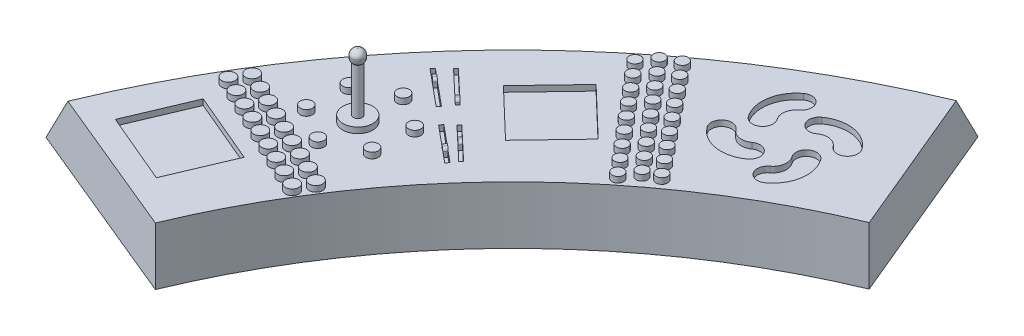
SolidWorks part; units mm, degrees
material "ABS"
ref_plane "Front Plane" through (0, 0, 0) normal (0, 0, 1) x (1, 0, 0)
ref_plane "Top Plane" through (0, 0, 0) normal (0, 1, 0) x (1, 0, 0)
ref_plane "Right Plane" through (0, 0, 0) normal (1, 0, 0) x (0, 0, -1)
sketch "Sketch1" plane through (0, 0, 0) normal (0, 1, 0) x (1, 0, 0)
  line L0 (0, 1495.54) -> (0, -1495.54) construction
  line L1 (0, 0) -> (1057.5065, 1057.5065) construction
  line L2 (1057.5065, 1057.5065) -> (-1057.5065, -1057.5065) construction
  line L3 (-1057.5065, -1057.5065) -> (1057.5065, -1057.5065) construction
  line L4 (1057.5065, -1057.5065) -> (-1057.5065, 1057.5065) construction
  line L5 (-1057.5065, 1057.5065) -> (1057.5065, 1057.5065) construction
  line L6 (440.104, -1057.5065) -> (574.625, -1380.7411)
  line L7 (440.104, 1057.5065) -> (574.625, 1380.7411)
  line L8 (-440.104, 1057.5065) -> (-574.625, 1380.7411)
  line L9 (-440.104, -1057.5065) -> (-574.625, -1380.7411)
  line L10 (-1058.4838, 437.7482) -> (-1382.0172, 571.5491)
  circle A0 centre (0, 0) radius 1495.54
  arc A2 (440.104, 1057.5065) -> (440.104, -1057.5065) centre (0, 0) cw
  arc A3 (-440.104, -1057.5065) -> (-440.104, 1057.5065) centre (0, 0) cw
  arc A4 (-440.104, 1057.5065) -> (-1058.4838, 437.7482) centre (0, 0) ccw
extrude "Boss-Extrude1" add sketch "Sketch1" along normal blind 100 contours L10 A3 L8 A0
chamfer "Chamfer1" distance 100 angle 35 1 edges at (-1058.6832, 100, -1056.3285) first distance on face at (-1018.5021, 50, -1016.2368)
sketch "Sketch2" plane through (0, 100, 0) normal (0, 1, 0) x (1, 0, 0)
  line L0 (-1248.8423, 558.6772) -> (-1125.6399, 506.5387)
  line L1 (-1248.8423, 558.6772) -> (-1203.5398, 665.7263)
  line L2 (-1125.6399, 506.5387) -> (-1080.3374, 613.5878)
  line L3 (-1203.5398, 665.7263) -> (-1080.3374, 613.5878)
extrude "Cut-Extrude1" cut sketch "Sketch2" against normal blind 10
sketch "Sketch3" plane through (0, 100, 0) normal (0, 1, 0) x (1, 0, 0)
  circle A0 centre (-1204.8141, 710.8155) radius 11.5832
  circle A1 centre (-1177.8503, 697.6643) radius 11.5832
  circle A2 centre (-1150.8865, 684.5132) radius 11.5832
  circle A3 centre (-1123.9226, 671.3621) radius 11.5832
  circle A4 centre (-1096.9588, 658.2109) radius 11.5832
  circle A5 centre (-1069.995, 645.0598) radius 11.5832
  circle A6 centre (-1043.0312, 631.9086) radius 11.5832
  circle A7 centre (-1016.0674, 618.7575) radius 11.5832
  circle A8 centre (-989.1035, 605.6064) radius 11.5832
  circle A9 centre (-1162.3991, 723.3793) radius 11.5832
  circle A10 centre (-1135.4353, 710.2282) radius 11.5832
  circle A11 centre (-1108.4715, 697.0771) radius 11.5832
  circle A12 centre (-1081.5077, 683.9259) radius 11.5832
  circle A13 centre (-1054.5439, 670.7748) radius 11.5832
  circle A14 centre (-1027.58, 657.6237) radius 11.5832
  circle A15 centre (-1000.6162, 644.4725) radius 11.5832
  circle A16 centre (-973.6524, 631.3214) radius 11.5832
  circle A17 centre (-1189.363, 736.5305) radius 11.5832
  dimension "D1" = 9
  dimension "D2" = 2
extrude "Boss-Extrude2" add sketch "Sketch3" along normal blind 10
sketch "Sketch4" plane through (0, 100, 0) normal (0, 1, 0) x (1, 0, 0)
  circle A0 centre (-1091.3889, 806.406) radius 10.7258
  circle A1 centre (-1028.8581, 837.8685) radius 10.7258
  circle A2 centre (-970.3453, 799.4465) radius 10.7258
  circle A3 centre (-974.3634, 729.5619) radius 10.7258
  circle A4 centre (-1036.8942, 698.0994) radius 10.7258
  circle A5 centre (-1095.407, 736.5214) radius 10.7258
  dimension "D1" = 6
extrude "Boss-Extrude3" add sketch "Sketch4" along normal blind 10
sketch "Sketch5" plane through (0, 100, 0) normal (0, 1, 0) x (1, 0, 0)
  line L4 (-1052.1599, 907.8326) -> (-989.7445, 856.0222)
  line L5 (-1052.1599, 907.8326) -> (-1047.9864, 912.8604)
  line L6 (-989.7445, 856.0222) -> (-985.571, 861.05)
  line L7 (-1047.9864, 912.8604) -> (-985.571, 861.05)
  line L8 (-960.2346, 830.6981) -> (-897.8192, 778.8877)
  line L9 (-960.2346, 830.6981) -> (-956.061, 835.7259)
  line L10 (-956.061, 835.7259) -> (-893.6456, 783.9155)
  line L11 (-897.8192, 778.8877) -> (-893.6456, 783.9155)
  dimension "D1" = 2
extrude "Cut-Extrude2" cut sketch "Sketch5" against normal blind 10
sketch "Sketch6" plane through (0, 100, 0) normal (0, 1, 0) x (1, 0, 0)
  line L0 (-1032.0136, 928.4032) -> (-975.4146, 874.9307)
  line L1 (-1032.0136, 928.4032) -> (-1027.9251, 932.7307)
  line L2 (-975.4146, 874.9307) -> (-971.3261, 879.2583)
  line L3 (-1027.9251, 932.7307) -> (-971.3261, 879.2583)
  line L4 (-944.2512, 846.5634) -> (-887.6521, 793.0909)
  line L5 (-944.2512, 846.5634) -> (-940.1627, 850.8909)
  line L6 (-940.1627, 850.8909) -> (-883.5637, 797.4185)
  line L7 (-887.6521, 793.0909) -> (-883.5637, 797.4185)
  dimension "D1" = 2
extrude "Cut-Extrude3" cut sketch "Sketch6" against normal blind 10
sketch "Sketch7" plane through (0, 90, 0) normal (0, 1, 0) x (1, 0, 0)
  line L0 (-1038.2772, 897.0031) -> (-1034.4449, 901.6197)
  line L1 (-1038.2772, 897.0031) -> (-1030.7236, 890.7329)
  line L2 (-1034.4449, 901.6197) -> (-1026.8913, 895.3496)
  line L3 (-1030.7236, 890.7329) -> (-1026.8913, 895.3496)
  line L4 (-985.571, 861.05) -> (-1047.9864, 912.8604) construction
  dimension "D1" = 6
extrude "Boss-Extrude5" add sketch "Sketch7" along normal blind 14
fillet "Fillet2" radius 5 1 edges at (-1028.8074, 104, -893.0413)
sketch "Sketch8" plane through (0, 90, 0) normal (0, 1, 0) x (1, 0, 0)
  line L0 (-920.5471, 806.2461) -> (-924.8533, 801.0584)
  line L1 (-920.5471, 806.2461) -> (-913.2442, 800.1841)
  line L2 (-924.8533, 801.0584) -> (-917.5505, 794.9964)
  line L3 (-913.2442, 800.1841) -> (-917.5505, 794.9964)
  line L4 (-893.6456, 783.9155) -> (-956.061, 835.7259) construction
extrude "Boss-Extrude6" add sketch "Sketch8" along normal blind 14
fillet "Fillet3" radius 5 1 edges at (-915.3973, 104, -797.5902)
sketch "Sketch9" plane through (0, 90, 0) normal (0, 1, 0) x (1, 0, 0)
  line L0 (-917.4233, 829.4076) -> (-921.5117, 825.0801)
  line L1 (-917.4233, 829.4076) -> (-910.5466, 822.9109)
  line L2 (-921.5117, 825.0801) -> (-914.6351, 818.5833)
  line L3 (-910.5466, 822.9109) -> (-914.6351, 818.5833)
  line L4 (-883.5637, 797.4185) -> (-940.1627, 850.8909) construction
  line L5 (-944.2512, 846.5634) -> (-887.6521, 793.0909) construction
extrude "Boss-Extrude7" add sketch "Sketch9" along normal blind 14
fillet "Fillet4" radius 5 1 edges at (-912.5909, 104, -820.7471)
sketch "Sketch10" plane through (0, 90, 0) normal (0, 1, 0) x (1, 0, 0)
  line L0 (-982.9956, 890.2831) -> (-987.0841, 885.9556)
  line L1 (-982.9956, 890.2831) -> (-976.2545, 883.9144)
  line L2 (-987.0841, 885.9556) -> (-980.343, 879.5868)
  line L3 (-976.2545, 883.9144) -> (-980.343, 879.5868)
  line L4 (-971.3261, 879.2583) -> (-1027.9251, 932.7307) construction
  line L5 (-1032.0136, 928.4032) -> (-975.4146, 874.9307) construction
extrude "Boss-Extrude8" add sketch "Sketch10" along normal blind 14
fillet "Fillet5" radius 5 1 edges at (-978.2987, 104, -881.7506)
sketch "Sketch11" plane through (0, 100, 0) normal (0, 1, 0) x (1, 0, 0)
  line L0 (-962.9727, 945.8833) -> (-879.042, 865.6407)
  line L1 (-962.9727, 945.8833) -> (-884.4013, 1028.0659)
  line L2 (-879.042, 865.6407) -> (-800.4706, 947.8234)
  line L3 (-884.4013, 1028.0659) -> (-800.4706, 947.8234)
extrude "Cut-Extrude4" cut sketch "Sketch11" against normal blind 10
sketch "Sketch12" plane through (0, 100, 0) normal (0, 1, 0) x (1, 0, 0)
  circle A0 centre (-878.5926, 1089.6189) radius 10
  circle A1 centre (-859.309, 1066.6376) radius 10
  circle A2 centre (-840.0253, 1043.6563) radius 10
  circle A3 centre (-820.7417, 1020.6749) radius 10
  circle A4 centre (-801.4581, 997.6936) radius 10
  circle A5 centre (-782.1745, 974.7123) radius 10
  circle A6 centre (-762.8908, 951.7309) radius 10
  circle A7 centre (-743.6072, 928.7496) radius 10
  circle A8 centre (-724.3236, 905.7683) radius 10
  circle A9 centre (-841.2545, 1090.5967) radius 10
  circle A10 centre (-821.9709, 1067.6153) radius 10
  circle A11 centre (-802.6873, 1044.634) radius 10
  circle A12 centre (-783.4036, 1021.6527) radius 10
  circle A13 centre (-764.12, 998.6713) radius 10
  circle A14 centre (-744.8364, 975.69) radius 10
  circle A15 centre (-725.5527, 952.7087) radius 10
  circle A16 centre (-706.2691, 929.7273) radius 10
  circle A17 centre (-860.5381, 1113.578) radius 10
  dimension "D1" = 9
  dimension "D2" = 2
extrude "Boss-Extrude9" add sketch "Sketch12" along normal blind 10
sketch "Sketch13" plane through (0, 100, 0) normal (0, 1, 0) x (1, 0, 0)
  circle A0 centre (-835.2815, 1128.5572) radius 10
  circle A1 centre (-816.4019, 1105.2429) radius 10
  circle A2 centre (-797.5222, 1081.9285) radius 10
  circle A3 centre (-778.6426, 1058.6141) radius 10
  circle A4 centre (-759.763, 1035.2997) radius 10
  circle A5 centre (-740.8834, 1011.9853) radius 10
  circle A6 centre (-722.0038, 988.671) radius 10
  circle A7 centre (-703.1242, 965.3566) radius 10
  circle A8 centre (-684.2446, 942.0422) radius 10
  dimension "D1" = 9
extrude "Boss-Extrude10" add sketch "Sketch13" along normal blind 10
sketch "Sketch15" plane through (0, 100, 0) normal (0, 1, 0) x (1, 0, 0)
  arc A0 (-680.3009, 1180.1983) -> (-689.4622, 1122.1462) centre (-655.8555, 1146.5917) ccw construction
  arc A1 (-690.8221, 1194.6625) -> (-703.9263, 1111.6251) centre (-655.8555, 1146.5917) ccw
  arc A2 (-669.7798, 1165.7342) -> (-674.9981, 1132.6674) centre (-655.8555, 1146.5917) ccw
  arc A3 (-669.7798, 1165.7342) -> (-690.8221, 1194.6625) centre (-680.3009, 1180.1983) ccw
  arc A4 (-703.9263, 1111.6251) -> (-674.9981, 1132.6674) centre (-689.4622, 1122.1462) ccw
  arc A5 (-571.0392, 1150.8408) -> (-629.0913, 1160.0021) centre (-604.6458, 1126.3954) ccw construction
  arc A6 (-556.575, 1161.362) -> (-639.6124, 1174.4662) centre (-604.6458, 1126.3954) ccw
  arc A7 (-585.5033, 1140.3196) -> (-618.5701, 1145.538) centre (-604.6458, 1126.3954) ccw
  arc A8 (-585.5033, 1140.3196) -> (-556.575, 1161.362) centre (-571.0392, 1150.8408) ccw
  arc A9 (-639.6124, 1174.4662) -> (-618.5701, 1145.538) centre (-629.0913, 1160.0021) ccw
  arc A10 (-600.3967, 1041.579) -> (-591.2354, 1099.6311) centre (-624.8421, 1075.1857) ccw construction
  arc A11 (-589.8755, 1027.1149) -> (-576.7713, 1110.1523) centre (-624.8421, 1075.1857) ccw
  arc A12 (-610.9179, 1056.0432) -> (-605.6996, 1089.11) centre (-624.8421, 1075.1857) ccw
  arc A13 (-610.9179, 1056.0432) -> (-589.8755, 1027.1149) centre (-600.3967, 1041.579) ccw
  arc A14 (-576.7713, 1110.1523) -> (-605.6996, 1089.11) centre (-591.2354, 1099.6311) ccw
  arc A15 (-709.6585, 1070.9366) -> (-651.6064, 1061.7753) centre (-676.0518, 1095.382) ccw construction
  arc A16 (-724.1226, 1060.4154) -> (-641.0852, 1047.3112) centre (-676.0518, 1095.382) ccw
  arc A17 (-695.1944, 1081.4577) -> (-662.1275, 1076.2394) centre (-676.0518, 1095.382) ccw
  arc A18 (-695.1944, 1081.4577) -> (-724.1226, 1060.4154) centre (-709.6585, 1070.9366) ccw
  arc A19 (-641.0852, 1047.3112) -> (-662.1275, 1076.2394) centre (-651.6064, 1061.7753) ccw
  point P3 (-696.9046, 1153.0697)
  point P13 (-598.1679, 1167.4444)
  point P21 (-583.7931, 1068.7077)
  point P29 (-682.5298, 1054.333)
  dimension "D1" = 4
extrude "Cut-Extrude5" cut sketch "Sketch15" against normal blind 10
sketch "Sketch16" plane through (0, 100, 0) normal (0, 1, 0) x (1, 0, 0)
  circle A0 centre (-1035.3341, 765.7253) radius 25.94
extrude "Boss-Extrude11" add sketch "Sketch16" along normal blind 10
ref_point "Point1"
sketch "Sketch18" plane through (0, 110, 0) normal (0, 1, 0) x (1, 0, 0)
  circle A0 centre (-1035.3341, 765.7253) radius 7.8307
extrude "Boss-Extrude12" add sketch "Sketch18" along normal blind 80
ref_point "Point2"
sketch "Sketch20" plane through (0, 190, 0) normal (0, 1, 0) x (1, 0, 0)
  circle A0 centre (-1035.3341, 765.7253) radius 10.8465
extrude "Boss-Extrude13" add sketch "Sketch20" along normal blind 20
fillet "Fillet6" radius 10 1 edges at (-1035.3341, 210, -754.8787)
fillet "Fillet7" radius 10 1 edges at (-1035.3341, 190, -754.8787)
